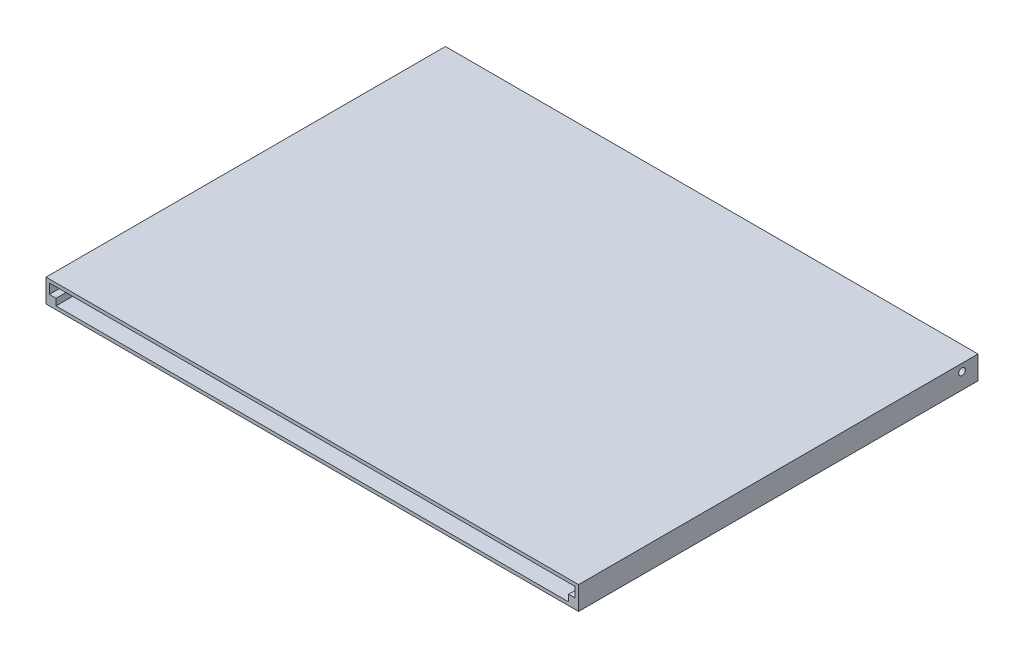
SolidWorks part; units mm, degrees
ref_plane "Front Plane" through (0, 0, 0) normal (0, 0, 1) x (1, 0, 0)
ref_plane "Top Plane" through (0, 0, 0) normal (0, 1, 0) x (1, 0, 0)
ref_plane "Right Plane" through (0, 0, 0) normal (1, 0, 0) x (0, 0, -1)
sketch "Sketch1" plane through (0, 0, 0) normal (0, 1, 0) x (1, 0, 0)
  line L1 (-254, 190.5) -> (254, 190.5)
  line L2 (-254, 190.5) -> (-254, -190.5)
  line L3 (-254, -190.5) -> (254, -190.5)
  line L4 (254, 190.5) -> (254, -190.5)
  line L5 (-254, 190.5) -> (254, -190.5) construction
  line L6 (-254, -190.5) -> (254, 190.5) construction
  point P0 (0, 0)
  dimension "D1" = 381
  dimension "D2" = 508
extrude "Boss-Extrude1" add sketch "Sketch1" along normal blind 22.225
sketch "Sketch2" plane through (0, 0, 190.5) normal (0, 0, 1) x (1, 0, 0)
  line L0 (-254, 22.225) -> (-254, 0) construction
  line L1 (250.825, 19.05) -> (-250.825, 19.05)
  line L2 (250.825, 19.05) -> (250.825, 3.175)
  line L3 (250.825, 3.175) -> (-250.825, 3.175)
  line L4 (-250.825, 19.05) -> (-250.825, 3.175)
  line L5 (250.825, 19.05) -> (-250.825, 3.175) construction
  line L6 (250.825, 3.175) -> (-250.825, 19.05) construction
  line L7 (254, 22.225) -> (254, 0) construction
  line L8 (-254, 22.225) -> (254, 22.225) construction
  line L9 (-254, 0) -> (254, 0) construction
  point P0 (0, 11.1125)
  dimension "D1" = 3.175
  dimension "D2" = 3.175
  dimension "D3" = 3.175
  dimension "D4" = 3.175
extrude "Cut-Extrude1" cut sketch "Sketch2" against normal blind 342.9
sketch "Sketch3" plane through (0, 0, 190.5) normal (0, 0, 1) x (1, 0, 0)
  line L0 (0, -55) -> (0, 55) construction
  line L1 (-250.825, 9.525) -> (-244.475, 9.525)
  line L2 (-250.825, 9.525) -> (-250.825, 3.175)
  line L3 (-250.825, 3.175) -> (-244.475, 3.175)
  line L4 (-244.475, 9.525) -> (-244.475, 3.175)
  line L13 (250.825, 3.175) -> (244.475, 3.175)
  line L14 (244.475, 9.525) -> (244.475, 3.175)
  line L15 (250.825, 9.525) -> (244.475, 9.525)
  line L16 (250.825, 9.525) -> (250.825, 3.175)
  point P5 (0, 0)
  point P6 (0, 0)
  dimension "D1" = 6.35
  dimension "D2" = 6.35
extrude "Boss-Extrude2" add sketch "Sketch3" against normal blind 35.56
sketch "Sketch4" plane through (-254, 0, 0) normal (-1, 0, 0) x (0, 0, 1)
  line L2 (-190.5, 0) -> (190.5, 0) construction
  line L3 (190.5, 22.225) -> (190.5, 0) construction
  circle A0 centre (-175.26, 15.24) radius 3.175
  dimension "D1" = 6.35
  dimension "D2" = 15.24
  dimension "D3" = 365.76
extrude "Cut-Extrude2" cut sketch "Sketch4" against normal blind 25.4
extrude "Cut-Extrude3" cut sketch "Sketch4<2>" along normal blind 25.4 from surface starting at face at (254, 11.1125, 0)
sketch "Sketch4<2>" plane through (-254, 0, 0) normal (-1, 0, 0) x (0, 0, 1) same geometry as "Sketch4"
